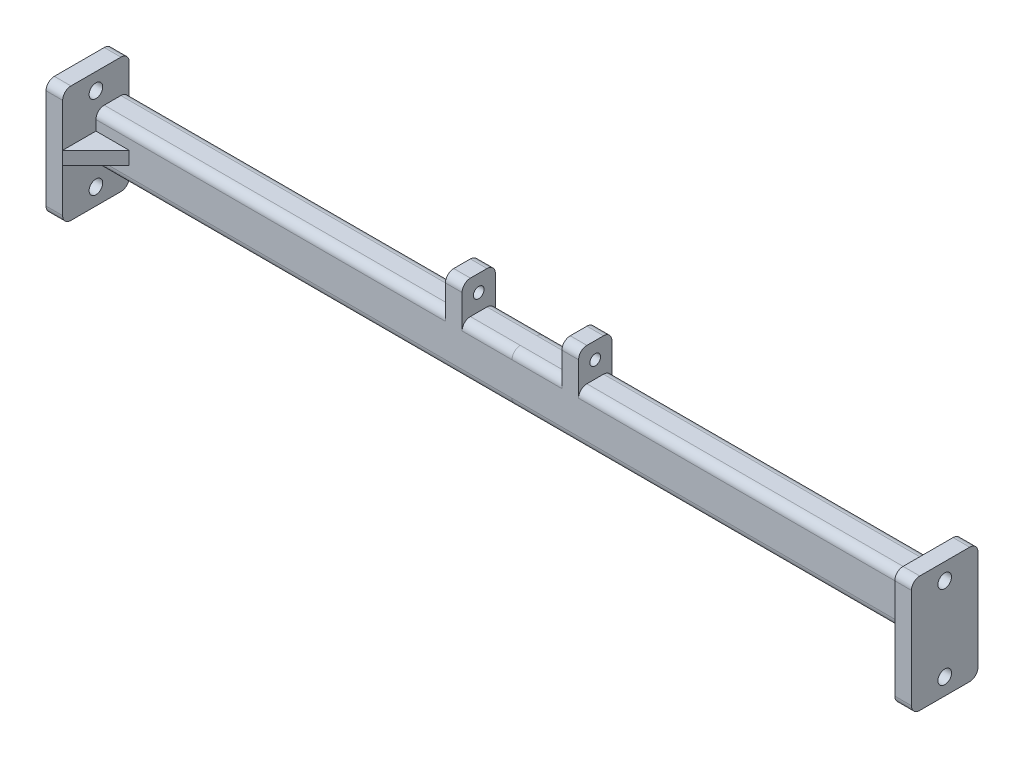
SolidWorks part; units mm, degrees
ref_plane "Plan de face" through (0, 0, 0) normal (0, 0, 1) x (1, 0, 0)
ref_plane "Plan de dessus" through (0, 0, 0) normal (0, 1, 0) x (1, 0, 0)
ref_plane "Plan de droite" through (0, 0, 0) normal (1, 0, 0) x (0, 0, -1)
sketch "Esquisse2" plane through (0, 0, 0) normal (0, 0, 1) x (1, 0, 0)
  line L0 (-99.6832, 0) -> (103.5672, 0) construction
  line L1 (0, 50.6843) -> (0, -58.1265) construction
  line L3 (125, 7.5) -> (125, 17.5)
  line L4 (125, 17.5) -> (130, 17.5)
  line L5 (130, 17.5) -> (130, -17.5)
  line L6 (130, 0) -> (0, 0)
  line L7 (0, -7.5) -> (0, 7.5)
  line L8 (0, 7.5) -> (15, 7.5)
  line L9 (15, 7.5) -> (15, 17.5)
  line L10 (15, 17.5) -> (20, 17.5)
  line L11 (20, 17.5) -> (20, 7.5)
  line L12 (20, 7.5) -> (125, 7.5)
  line L13 (20, -17.5) -> (20, -7.5)
  line L14 (15, -17.5) -> (20, -17.5)
  line L15 (15, -7.5) -> (15, -17.5)
  line L16 (0, -7.5) -> (15, -7.5)
  line L17 (125, -17.5) -> (130, -17.5)
  line L18 (125, -7.5) -> (125, -17.5)
  line L19 (20, -7.5) -> (125, -7.5)
  line L20 (15, -7.5) -> (20, -7.5)
  dimension "D1" = 130
  dimension "D2" = 5
  dimension "D3" = 5
  dimension "D4" = 7.5
  dimension "D5" = 15
  dimension "D6" = 10
  dimension "D7" = 10
extrude "Boss.-Extru.1" add sketch "Esquisse2" along normal blind 10 contours L12 L11 L10 L9 L8 L7 L6 L5 L4 L3 | L13 L19 L18 L17 L5 L6 L7 L16 L15 L14 region at (65.6977, 4.564, 0) region at (68.0488, -4.1768, 0)
sketch "Esquisse3" plane through (0, 0, 10) normal (0, 0, 1) x (1, 0, 0)
  line L0 (125, 7.5) -> (125, -7.5)
  line L16 (125, 7.5) -> (20, 7.5)
  line L17 (20, 7.5) -> (20, 17.5)
  line L18 (20, 17.5) -> (15, 17.5)
  line L19 (15, 17.5) -> (15, 7.5)
  line L20 (15, 7.5) -> (0, 7.5)
  line L21 (0, 7.5) -> (0, -7.5)
  line L22 (0, -7.5) -> (125, -7.5)
  line L27 (125, -7.5) -> (125, -17.5)
  line L28 (125, -17.5) -> (130, -17.5)
  line L29 (130, -17.5) -> (130, 17.5)
  line L30 (130, 17.5) -> (125, 17.5)
  line L31 (125, 17.5) -> (125, 7.5)
  line L32 (125, 7.5) -> (20, 7.5)
  line L33 (20, 7.5) -> (20, 17.5)
  line L34 (20, 17.5) -> (15, 17.5)
  line L35 (15, 17.5) -> (15, 7.5)
  line L36 (15, 7.5) -> (0, 7.5)
  line L37 (0, 7.5) -> (0, -7.5)
  line L38 (0, -7.5) -> (125, -7.5)
  line L43 (125, -7.5) -> (125, -17.5)
  line L44 (125, -17.5) -> (130, -17.5)
  line L45 (130, -17.5) -> (130, 17.5)
  line L46 (130, 17.5) -> (125, 17.5)
  line L47 (125, 17.5) -> (125, 7.5)
  line M28 (125, -7.5) -> (125, -17.5)
  line M29 (125, -17.5) -> (130, -17.5)
  line M30 (130, -17.5) -> (130, 17.5)
  line M31 (130, 17.5) -> (125, 17.5)
  line M32 (125, 17.5) -> (125, 7.5)
  dimension "D1" = 0
extrude "Boss.-Extru.2" add sketch "Esquisse3" along normal blind 10 contours L0 M32 M28 M29 M30 M31 region at (127.5, 0, 10)
sketch "Esquisse4" plane through (15, 0, 0) normal (-1, 0, 0) x (0, 0, 1)
  line L0 (5, 17.5) -> (5, 7.5) construction
  line L4 (0, 17.5) -> (0, 7.5)
  line L5 (0, 7.5) -> (10, 7.5)
  line L6 (10, 7.5) -> (10, 17.5)
  line L7 (10, 17.5) -> (0, 17.5)
  line L8 (0, 17.5) -> (0, 7.5)
  line L9 (0, 7.5) -> (10, 7.5)
  line L10 (10, 7.5) -> (10, 17.5)
  line L11 (10, 17.5) -> (0, 17.5)
  circle A0 centre (5, 12.5) radius 1.6
  dimension "D2" = 3.2
  dimension "D3" = 5
  dimension "D1" = 0
extrude "Enlèv. mat.-Extru.1" cut sketch "Esquisse4" against normal blind 15 contours A0
sketch "Esquisse5" plane through (125, 0, 0) normal (-1, 0, 0) x (0, 0, 1)
  line L0 (-10.6824, 0) -> (40.9879, 0) construction
  line L1 (10, 17.5) -> (10, -17.5) construction
  line L8 (0, 17.5) -> (0, 7.5)
  line L9 (0, 7.5) -> (10, 7.5)
  line L10 (10, 7.5) -> (10, -7.5)
  line L11 (10, -7.5) -> (0, -7.5)
  line L12 (0, -7.5) -> (0, -17.5)
  line L13 (0, -17.5) -> (20, -17.5)
  line L14 (20, -17.5) -> (20, 17.5)
  line L15 (20, 17.5) -> (0, 17.5)
  line L16 (0, 17.5) -> (0, 7.5)
  line L17 (0, 7.5) -> (10, 7.5)
  line L18 (10, 7.5) -> (10, -7.5)
  line L19 (10, -7.5) -> (0, -7.5)
  line L20 (0, -7.5) -> (0, -17.5)
  line L21 (0, -17.5) -> (20, -17.5)
  line L22 (20, -17.5) -> (20, 17.5)
  line L23 (20, 17.5) -> (0, 17.5)
  circle A0 centre (10, 12.5) radius 2.05
  circle A1 centre (10, -12.5) radius 2.05
  dimension "D2" = 4.1
  dimension "D3" = 12.5
  dimension "D1" = 0
extrude "Enlèv. mat.-Extru.2" cut sketch "Esquisse5" against normal blind 15 contours A0 | A1
fillet "Congé1" radius 2.5 12 edges at (62.5, -7.5, 0) (127.5, -17.5, 0) (127.5, -17.5, 20) (127.5, 17.5, 0) (127.5, 17.5, 20) (62.5, -7.5, 10) (17.5, 17.5, 0) (17.5, 17.5, 10) (7.5, 7.5, 10) (72.5, 7.5, 10) (7.5, 7.5, 0) (72.5, 7.5, 0)
sketch "Esquisse6" plane through (125, 0, 0) normal (-1, 0, 0) x (0, 0, 1)
  line L0 (10, 2) -> (20, 2)
  line L1 (0, 0) -> (34.0911, 0) construction
  line L2 (10, -2) -> (20, -2)
  line L8 (0, -5) -> (0, -15)
  line L9 (2.5, -17.5) -> (17.5, -17.5)
  line L10 (20, -15) -> (20, 15)
  line L11 (17.5, 17.5) -> (2.5, 17.5)
  line L12 (0, 15) -> (0, 5)
  line L13 (2.5, 7.5) -> (7.5, 7.5)
  line L14 (10, 5) -> (10, -5)
  line L15 (7.5, -7.5) -> (2.5, -7.5)
  line L16 (0, -5) -> (0, -15)
  line L17 (2.5, -17.5) -> (17.5, -17.5)
  line L18 (20, -15) -> (20, 15)
  line L19 (17.5, 17.5) -> (2.5, 17.5)
  line L20 (0, 15) -> (0, 5)
  line L21 (2.5, 7.5) -> (7.5, 7.5)
  line L22 (10, 5) -> (10, -5)
  line L23 (7.5, -7.5) -> (2.5, -7.5)
  arc A8 (0, -15) -> (2.5, -17.5) centre (2.5, -15) ccw
  arc A9 (17.5, -17.5) -> (20, -15) centre (17.5, -15) ccw
  arc A10 (20, 15) -> (17.5, 17.5) centre (17.5, 15) ccw
  arc A11 (2.5, 17.5) -> (0, 15) centre (2.5, 15) ccw
  arc A12 (2.5, 7.5) -> (0, 5) centre (2.5, 5) ccw
  arc A13 (10, 5) -> (7.5, 7.5) centre (7.5, 5) ccw
  arc A14 (7.5, -7.5) -> (10, -5) centre (7.5, -5) ccw
  arc A15 (0, -5) -> (2.5, -7.5) centre (2.5, -5) ccw
  arc A16 (0, -15) -> (2.5, -17.5) centre (2.5, -15) ccw
  arc A17 (17.5, -17.5) -> (20, -15) centre (17.5, -15) ccw
  arc A18 (20, 15) -> (17.5, 17.5) centre (17.5, 15) ccw
  arc A19 (2.5, 17.5) -> (0, 15) centre (2.5, 15) ccw
  arc A20 (2.5, 7.5) -> (0, 5) centre (2.5, 5) ccw
  arc A21 (10, 5) -> (7.5, 7.5) centre (7.5, 5) ccw
  arc A22 (7.5, -7.5) -> (10, -5) centre (7.5, -5) ccw
  arc A23 (0, -5) -> (2.5, -7.5) centre (2.5, -5) ccw
  line M25 (20, -15) -> (20, 15)
  line M33 (10, 5) -> (10, -5)
  dimension "D2" = 4
  dimension "D3" = 10
  dimension "D1" = 0
extrude "Boss.-Extru.3" add sketch "Esquisse6" along normal blind 10 contours L1 L18 L0 M33 | L1 L22 L2 M25 region at (125, 1, 15) region at (125, -1, 15)
chamfer "Chanfrein1" distance 10 angle 45 1 edges at (115, 0, 20)
mirror "Symétrie1" about plane through (0, 0, 0) normal (1, 0, 0) of "Chanfrein1", "Boss.-Extru.3", "Congé1", "Enlèv. mat.-Extru.2", "Enlèv. mat.-Extru.1", "Boss.-Extru.2", "Boss.-Extru.1"
